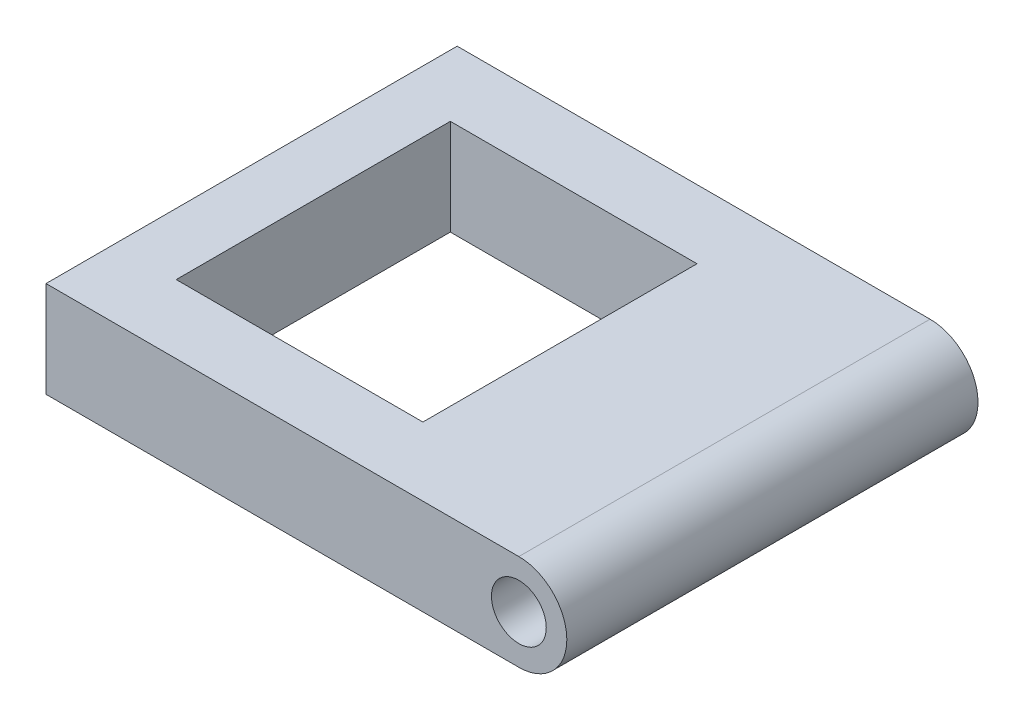
SolidWorks part; units mm, degrees
ref_plane "前视基准面" through (0, 0, 0) normal (0, 0, 1) x (1, 0, 0)
ref_plane "上视基准面" through (0, 0, 0) normal (0, 1, 0) x (1, 0, 0)
ref_plane "右视基准面" through (0, 0, 0) normal (1, 0, 0) x (0, 0, -1)
other "Configuration Table"
sketch "草图1" plane through (0, 0, 0) normal (0, 1, 0) x (1, 0, 0)
  line L0 (0, 0) -> (55, 0)
  line L2 (0, 0) -> (0, 60)
  line L3 (0, 60) -> (55, 60)
  line L4 (55, 0) -> (55, 60)
  line L6 (9, 10) -> (9, 50)
  line L7 (9, 50) -> (45, 50)
  line L8 (45, 50) -> (45, 10)
  line L9 (45, 10) -> (9, 10)
extrude "凸台-拉伸1" add sketch "草图1" along normal blind 14
sketch "草图2" plane through (0, 0, 0) normal (0, 0, 1) x (1, 0, 0)
  line L0 (55, 14) -> (69, 14)
  line L1 (55, 0) -> (69, 0)
  line L2 (55, 14) -> (55, 0)
  arc A0 (69, 0) -> (69, 14) centre (69, 7) ccw
  circle A1 centre (69, 7) radius 4
extrude "凸台-拉伸2" add sketch "草图2" against normal blind 60
